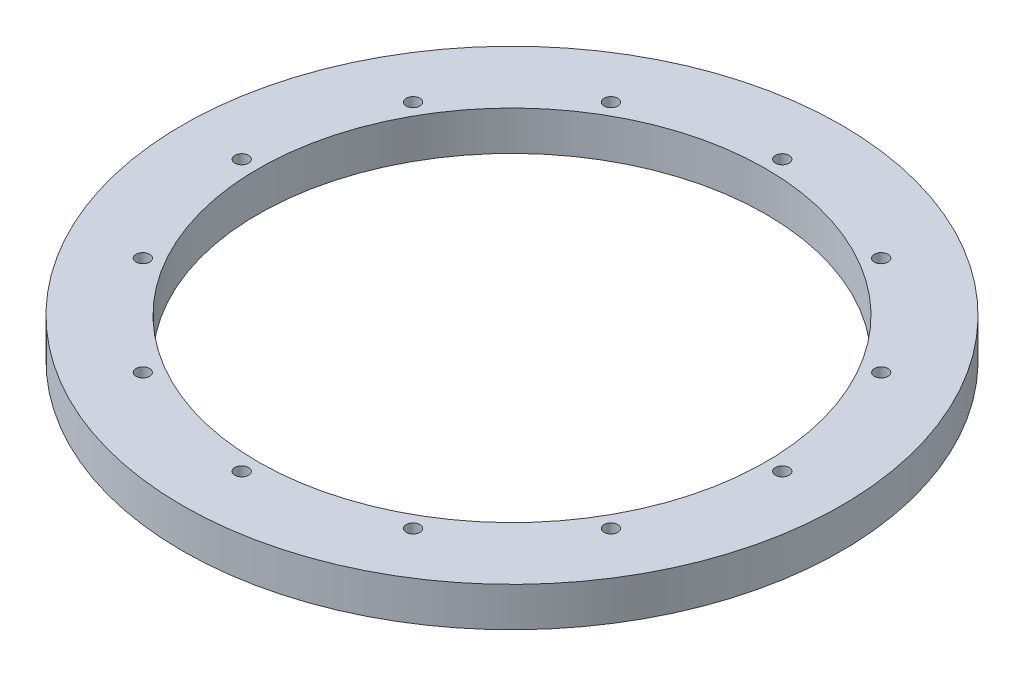
SolidWorks part; units mm, degrees
material "6061 Alloy"
ref_plane "Front Plane" through (0, 0, 0) normal (0, 0, 1) x (1, 0, 0)
ref_plane "Top Plane" through (0, 0, 0) normal (0, 1, 0) x (1, 0, 0)
ref_plane "Right Plane" through (0, 0, 0) normal (1, 0, 0) x (0, 0, -1)
sketch "Sketch1" plane through (0, 0, 0) normal (0, 1, 0) x (1, 0, 0)
  circle A0 centre (0, 0) radius 49.2125
  circle A1 centre (0, 0) radius 63.881
  circle A3 centre (0, -52.3875) radius 1.3208
  circle A4 centre (-26.1938, -45.3689) radius 1.3208
  circle A5 centre (-45.3689, -26.1937) radius 1.3208
  circle A6 centre (-52.3875, 0) radius 1.3208
  circle A7 centre (-45.3689, 26.1938) radius 1.3208
  circle A8 centre (-26.1937, 45.3689) radius 1.3208
  circle A9 centre (0, 52.3875) radius 1.3208
  circle A10 centre (26.1938, 45.3689) radius 1.3208
  circle A11 centre (45.3689, 26.1937) radius 1.3208
  circle A12 centre (52.3875, 0) radius 1.3208
  circle A13 centre (45.3689, -26.1938) radius 1.3208
  circle A14 centre (26.1937, -45.3689) radius 1.3208
  point P21 (0, 0)
  dimension "D1" = 98.425
  dimension "D4" = 2.6416
  dimension "D5" = 52.3875
  dimension "D2" = 14.6685
  dimension "D6" = 12
extrude "Boss-Extrude1" add sketch "Sketch1" along normal blind 7.62 contours A0 | A1 region at (-62.0742, 0, 0)
equation "\"Middle Coupler Inner Daimeter\"= 3.875in"
equation "\"Middle Coupler  Wall Thickness\" = 0.25in"
equation "\"Middle Coupler Bottom Thickness\"= 0.2in"
equation "\"Bearing Rail Offset\"= 0.45in"
equation "\"3-56 UNF Tap\"= 0.089in"
equation "\"3-56 UNF Clearance\"= 0.104in"
equation "\"D5@Sketch1\"=(\"Middle Coupler Inner Daimeter\"*2+0.5)/4in"
equation "\"Ball Bearing Distance\"= 0.03in"
equation "\"D4@Sketch1\"=\"3-56 UNF Clearance\""
equation "\"D1@Sketch1\"=\"Middle Coupler Inner Daimeter\""
equation "\"TCA Outer Diameter\" = 6in"
equation "\"Interstage Aeroframe Wall Thickness\" = 0.072in"
equation "\"Compression Spring OD\"= 0.42in"
equation "\"10-24 Tap\"= 0.157in"
equation "\"10-24 Clearance\"= 0.196in"
equation "\"Lower Stage Fuselage Wall Thickness\" = 0.25in"
equation "\"6-32 Tap\" = 0.107in"
equation "\"1/4-20 Tap\" = 0.201in"
equation "\"D2@Sketch1\"=0.5875 - 10/1000"
